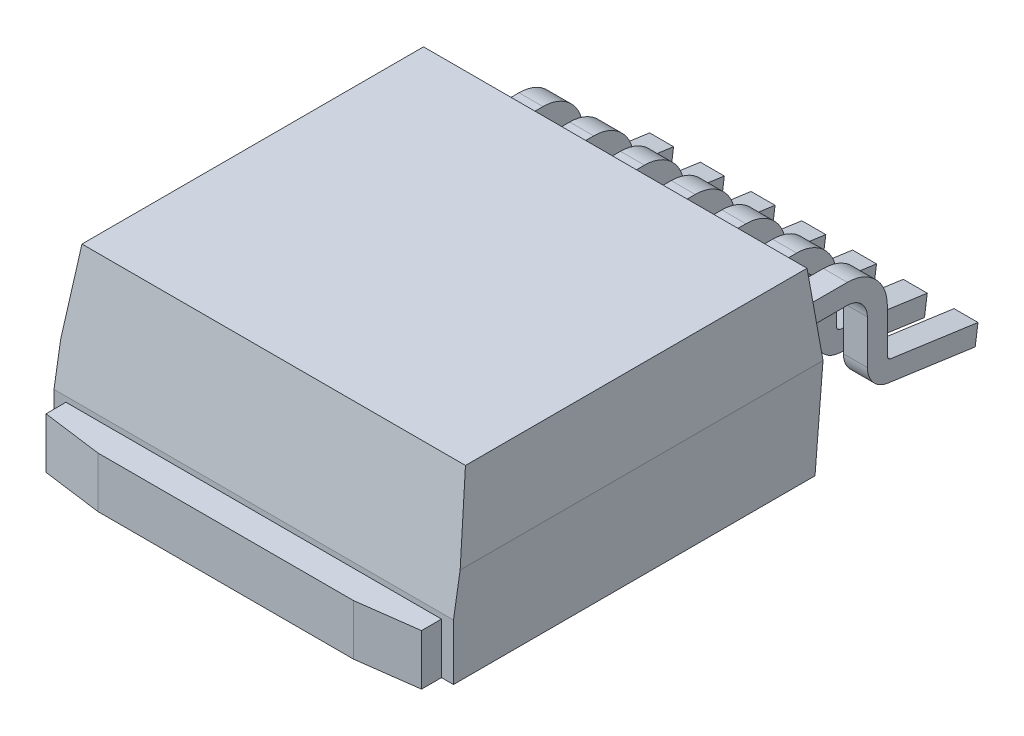
SolidWorks part; units mm, degrees
ref_plane "Front Plane" through (0, 0, 0) normal (0, 0, 1) x (1, 0, 0)
ref_plane "Top Plane" through (0, 0, 0) normal (0, 1, 0) x (1, 0, 0)
ref_plane "Right Plane" through (0, 0, 0) normal (1, 0, 0) x (0, 0, -1)
sketch "MB" plane through (0, 0, 0) normal (1, 0, 0) x (0, 0, -1)
  line L1 (4.525, 4.4) -> (-4.025, 4.4)
  line L3 (-4.525, 0) -> (4.525, 0)
  line L4 (-4.025, 4.4) -> (-4.525, 1.4)
  line L5 (-4.525, 1.4) -> (-4.525, 0)
  line L6 (4.525, 4.4) -> (4.725, 2.4)
  line L7 (4.725, 2.4) -> (4.525, 0)
  line L8 (4.525, 4.4) -> (4.525, 0) construction
  line L9 (4.725, 2.4) -> (4.525, 2.4) construction
  line L10 (-4.525, 1.4) -> (-4.025, 1.4) construction
  line L11 (-4.025, 1.4) -> (-4.025, 4.4) construction
  dimension "D1" = 0.2
  dimension "D2" = 2
  dimension "D3" = 2.4
  dimension "D4" = 1.4
  dimension "D5" = 9.25
  dimension "D6" = 0.5
  dimension "D7" = 4.4
extrude "MAIN BODY" add sketch "MB" along normal mid plane 10
sketch "ICP CUT" plane through (0, 0, 0) normal (0, -1, 0) x (-1, 0, 0)
  line L5 (-5, -4.525) -> (5, -4.525) construction
  line L6 (4.25, -4.525) -> (-4.25, -4.525)
  line L8 (4.25, -4.525) -> (4.25, 2.325)
  line L9 (4.25, 2.325) -> (-4.25, 2.325)
  line L10 (-4.25, -4.525) -> (-4.25, 2.325)
  line L11 (-5, -4.525) -> (-5, 4.525) construction
  line L13 (-5, 4.525) -> (5, 4.525) construction
  point P11 (0, -4.525)
  dimension "D1" = 0.75
  dimension "D2" = 8.5
  dimension "D3" = 2.2
  dimension "D4" = 6.85
extrude "BACK IC PLATE CUT" cut sketch "ICP CUT" against normal blind 1.27
sketch "ICP" plane through (0, 1.27, 0) normal (0, -1, 0) x (1, 0, 0)
  line L0 (-4.25, 4.525) -> (-4.7, 4.525)
  line L1 (-4.7, 4.525) -> (-4.7, 5.025)
  line L2 (-4.7, 5.025) -> (-3.2, 5.225)
  line L3 (-3.2, 5.225) -> (3.2, 5.225)
  line L4 (-4.25, 4.525) -> (-4.25, -2.325)
  line L5 (-4.25, -2.325) -> (4.25, -2.325)
  line L6 (4.25, -2.325) -> (4.25, 4.525)
  line L7 (4.25, 4.525) -> (-4.25, 4.525)
  line L8 (-4.25, 4.525) -> (-4.25, -2.325)
  line L9 (-4.25, -2.325) -> (4.25, -2.325)
  line L12 (0, 5.225) -> (0, -2.325) construction
  line L13 (-4.25, -2.325) -> (4.25, -2.325) construction
  line L14 (-4.25, 4.525) -> (-5, 4.525) construction
  line L15 (-5, 4.525) -> (-5, -4.525) construction
  line L16 (4.25, 4.525) -> (-4.25, 4.525) construction
  line L17 (4.25, 4.525) -> (4.25, -2.325)
  line L18 (4.7, 5.025) -> (3.2, 5.225)
  line L19 (4.7, 4.525) -> (4.7, 5.025)
  line L20 (4.25, 4.525) -> (4.7, 4.525)
  dimension "D2" = 0.3
  dimension "D3" = 0.7
  dimension "D4" = 7.55
  dimension "D5" = 0.2
  dimension "D6" = 1.5
  dimension "D7" = 3.2
  dimension "D1" = 0
extrude "BACK IC PLATE" add sketch "ICP" along normal up to surface (1.27 mm away) separate body up to face at (0, 0, 0.55)
sketch "Sketch3" plane through (0, 0, 0) normal (1, 0, 0) x (0, 0, -1)
  line L0 (4.725, 2.4) -> (6.225, 2.4)
  line L1 (6.725, 1.9) -> (6.725, 0.801)
  line L2 (7.2415, 0.2069) -> (9.425, -0.1)
  line L3 (-4.525, 0) -> (4.525, 0) construction
  arc A0 (6.225, 2.4) -> (6.725, 1.9) centre (6.225, 1.9) cw
  arc A1 (6.725, 0.801) -> (7.2415, 0.2069) centre (7.325, 0.801) ccw
  dimension "D3" = 0.5
  dimension "D4" = 2
  dimension "D7" = 0.6
  dimension "D1" = 4.7
  dimension "D2" = 8
  dimension "D5" = 2.7
  dimension "D6" = 0.1
extrude "IC LEG" add sketch "Sketch3" along normal mid plane 0.6 separate body thin thin type one direction reverse wall 0.5
sketch "LC" plane through (0, 0, -4.725) normal (0, 0, 1) x (1, 0, 0)
  line L4 (-0.3, 2.9) -> (-0.3, 2.4)
  line L5 (-0.3, 2.4) -> (0.3, 2.4)
  line L6 (0.3, 2.4) -> (0.3, 2.9)
  line L7 (0.3, 2.9) -> (-0.3, 2.9)
  line L8 (-0.3, 2.9) -> (-0.3, 2.4)
  line L9 (-0.3, 2.4) -> (0.3, 2.4)
  line L10 (0.3, 2.4) -> (0.3, 2.9)
  line L11 (0.3, 2.9) -> (-0.3, 2.9)
  dimension "D1" = 0
extrude "IC LEG JOINT COMPLETION" add sketch "LC" along normal up to next separate body
sketch "CD" plane through (0, 4.4, 0) normal (0, 1, 0) x (1, 0, 0)
  line L0 (0, 4.525) -> (0, 4.725) construction
  line L1 (5, 4.525) -> (-5, 4.525) construction
  line L3 (5, 4.725) -> (-5, 4.725) construction
  dimension "CHAMFER DEPTH" = 0.2
sketch "CHAMFER CUTS" plane through (0, 0, 0) normal (0, 0, 1) x (1, 0, 0)
  line L0 (4.8, 4.4) -> (5, 4.4)
  line L1 (5, 4.4) -> (5, 2.4)
  line L2 (5, 2.4) -> (4.8, 4.4)
  line L3 (5, 0) -> (5, 2.4) construction
  line L4 (5, 2.4) -> (-5, 2.4) construction
  dimension "D1" = 0.2
extrude "SIDE CHAMFER" cut sketch "CHAMFER CUTS" against normal through all both and the other way through all
mirror "SC M" about plane through (0, 0, 0) normal (1, 0, 0) of "SIDE CHAMFER"
pattern_linear "LP IC LEGS" count 4 spacing 1.27 along (1, 0, 0) count 4 spacing 1.27 along (-1, 0, 0) of "IC LEG", "IC LEG JOINT COMPLETION" pattern seed only yes
equation "\"D1@CHAMFER CUTS\" = \"CHAMFER DEPTH@CD\""
